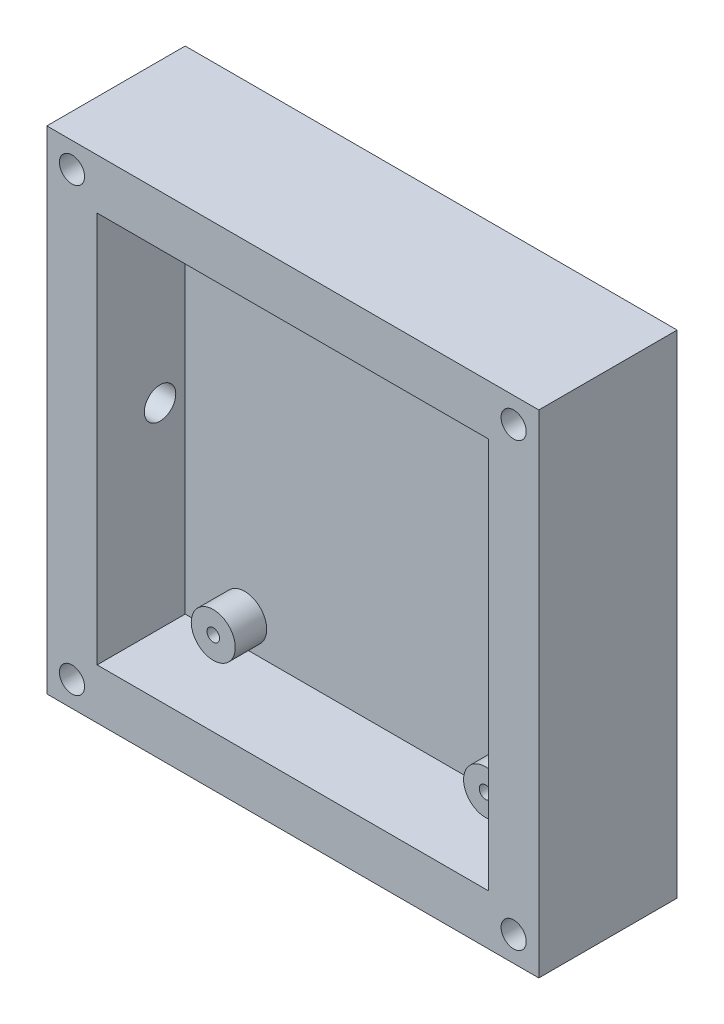
SolidWorks part; units mm, degrees
ref_plane "Plan de face" through (0, 0, 0) normal (0, 0, 1) x (1, 0, 0)
ref_plane "Plan de dessus" through (0, 0, 0) normal (0, 1, 0) x (1, 0, 0)
ref_plane "Plan de droite" through (0, 0, 0) normal (1, 0, 0) x (0, 0, -1)
sketch "Esquisse1" plane through (0, 0, 0) normal (0, 0, 1) x (1, 0, 0)
  line L0 (-39.11, 0) -> (39.11, 0) construction
  line L1 (-39.11, 39.11) -> (39.11, 39.11)
  line L2 (-39.11, 39.11) -> (-39.11, -39.11)
  line L3 (-39.11, -39.11) -> (39.11, -39.11)
  line L4 (39.11, 39.11) -> (39.11, -39.11)
  line L5 (-39.11, 39.11) -> (39.11, -39.11) construction
  line L6 (-39.11, -39.11) -> (39.11, 39.11) construction
  line L7 (39.11, 0) -> (0, 39.11) construction
  line L8 (0, 39.11) -> (0, -39.11) construction
  point P0 (0, 0)
  dimension "D1" = 78.22
  dimension "D2" = 78.22
extrude "Boss.-Extru.1" add sketch "Esquisse1" along normal blind 22
shell "Coque1" thickness 8 removed face at (0, 0, 22)
sketch "Esquisse2" plane through (0, 0, 22) normal (0, 0, 1) x (1, 0, 0)
  line L0 (-39.11, 39.11) -> (-31.11, 31.11) construction
  line L1 (-39.11, 39.11) -> (-39.11, -39.11) construction
  line L2 (39.11, 39.11) -> (-39.11, 39.11) construction
  line L3 (-39.11, 0) -> (39.11, 0) construction
  line L4 (39.11, -39.11) -> (39.11, 39.11) construction
  line L5 (39.11, 39.11) -> (-39.11, -39.11) construction
  circle A0 centre (-35.11, 35.11) radius 2
  circle A1 centre (35.11, -35.11) radius 2
  circle A2 centre (35.11, 35.11) radius 2
  circle A3 centre (-35.11, -35.11) radius 2
  dimension "D3" = 4
  dimension "D1" = 4
  dimension "D2" = 4
extrude "Enlèv. mat.-Extru.1" cut sketch "Esquisse2" against normal blind 14
sketch "Esquisse3" plane through (0, 0, 8) normal (0, 0, 1) x (1, 0, 0)
  line L3 (-24.4, 0) -> (24.4, 0) construction
  line L4 (-24.4, 29.5) -> (24.4, 29.5)
  line L5 (-24.4, 29.5) -> (-24.4, -29.5)
  line L6 (-24.4, -29.5) -> (24.4, -29.5)
  line L7 (24.4, 29.5) -> (24.4, -29.5)
  line L8 (-24.4, 29.5) -> (24.4, -29.5) construction
  line L9 (-24.4, -29.5) -> (24.4, 29.5) construction
  line L10 (0, 29.5) -> (0, -29.5) construction
  circle A0 centre (-21.65, 26.75) radius 1
  circle A1 centre (-21.65, -26.75) radius 1
  circle A2 centre (21.65, -26.75) radius 1
  circle A3 centre (21.65, 26.75) radius 1
  circle A4 centre (-21.65, 26.75) radius 3.5
  circle A5 centre (-21.65, -26.75) radius 3.5
  circle A6 centre (21.65, -26.75) radius 3.5
  circle A7 centre (21.65, 26.75) radius 3.5
  point P7 (0, 0)
  dimension "D3" = 2
  dimension "D6" = 2.5
  dimension "D1" = 48.8
  dimension "D2" = 59
  dimension "D4" = 2.75
  dimension "D5" = 2.75
extrude "Boss.-Extru.2" add sketch "Esquisse3" along normal blind 5 contours A7 | A6 | A5 | A4
extrude "Enlèv. mat.-Extru.3" cut sketch "Esquisse3<4>" along normal blind 5 contours A1 | A0 | A2 | A3
sketch "Esquisse3<4>" plane through (0, 0, 8) normal (0, 0, 1) x (1, 0, 0) same geometry as "Esquisse3"
sketch "Esquisse6" plane through (-39.11, 0, 0) normal (-1, 0, 0) x (0, 0, 1)
  line L0 (0, 39.11) -> (22, -39.11) construction
  line L1 (22, -39.11) -> (22, 0) construction
  line L2 (22, 39.11) -> (22, -39.11) construction
  line L3 (22, 0) -> (0, 0) construction
  line L4 (0, 0) -> (11, -39.11) construction
  line L5 (22, -39.11) -> (0, -39.11) construction
  line L6 (11, -39.11) -> (11, 39.11) construction
  line L7 (22, 39.11) -> (0, 39.11) construction
  circle A0 centre (12, -0.0403) radius 2.5
  dimension "D1" = 5
  dimension "D2" = 10
extrude "Enlèv. mat.-Extru.4" cut sketch "Esquisse6" against normal blind 12
